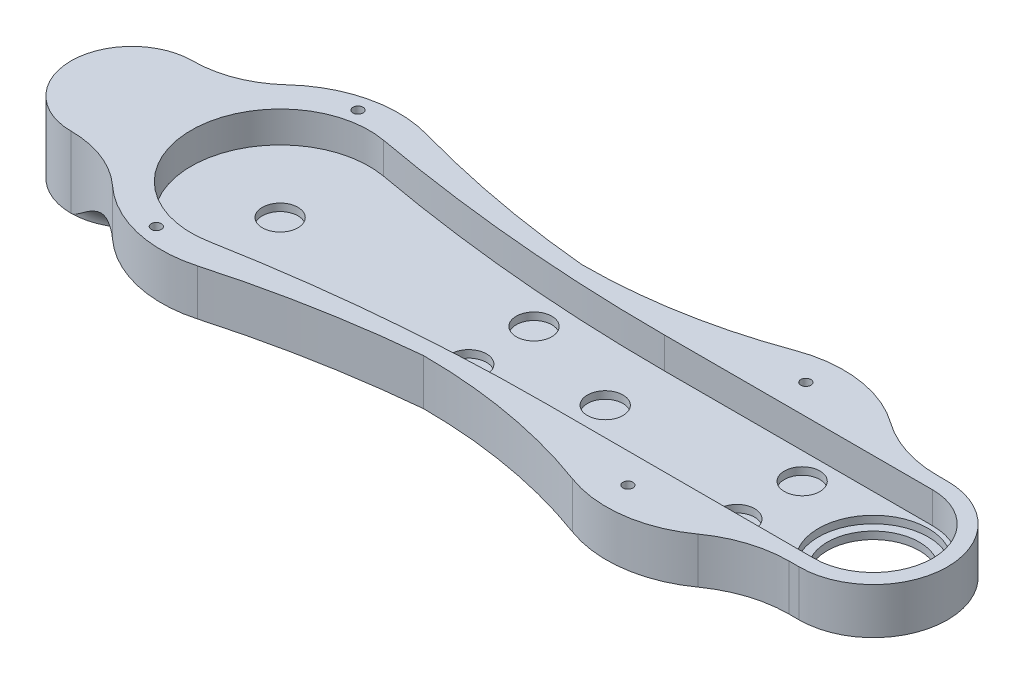
SolidWorks part; units mm, degrees
ref_plane "Front Plane" through (0, 0, 0) normal (0, 0, 1) x (1, 0, 0)
ref_plane "Top Plane" through (0, 0, 0) normal (0, 1, 0) x (1, 0, 0)
ref_plane "Right Plane" through (0, 0, 0) normal (1, 0, 0) x (0, 0, -1)
sketch "Sketch1" plane through (0, 0, 0) normal (0, 1, 0) x (1, 0, 0)
  line L0 (0, 0) -> (200, 0) construction
  line L1 (109.6, 25) -> (109.6, -25) construction
  line L2 (200, 25) -> (109.6, 25)
  line L3 (200, -25) -> (109.6, -25)
  line L4 (109.6, 20) -> (109.6, -20) construction
  line L5 (200, 20) -> (109.6, 20)
  line L6 (200, -20) -> (109.6, -20)
  circle A0 centre (0, 0) radius 30
  circle A1 centre (0, 0) radius 40
  circle A2 centre (109.6, 0) radius 25 construction
  circle A3 centre (200, 0) radius 25
  arc A4 (109.6, 25) -> (10.7476, 38.5291) centre (109.6, 392.9053) cw
  arc A5 (109.6, -25) -> (10.7476, -38.5291) centre (109.6, -392.9053) ccw
  circle A6 centre (109.6, 0) radius 20 construction
  circle A7 centre (200, 0) radius 20
  arc A8 (109.6, 20) -> (5.4293, 29.5046) centre (109.6, 595.608) cw
  arc A9 (109.6, -20) -> (5.4293, -29.5046) centre (109.6, -595.608) ccw
  dimension "D1" = 60
  dimension "D2" = 80
  dimension "D4" = 90.4
  dimension "D5" = 50
  dimension "D7" = 40
  dimension "D3" = 200
  dimension "D6" = 109.6
extrude "Boss-Extrude1" add sketch "Sketch1" along normal blind 10.5 contours A1 A9 A0 A8 | A8 L5 A3 L2 A4 A1 | L6 A9 A1 A5 L3 A3 | A7 L6 A3 L5 region at (100.5968, 0, -24.4026) region at (217.2249, 0, -17.2249) region at (21.2475, 0, -32.6216) region at (100.5968, 0, 24.4026)
sketch "Sketch4" plane through (0, 0, 0) normal (0, -1, 0) x (1, 0, 0)
  line L0 (200, 25) -> (109.6, 25) construction
  line L1 (200, -25) -> (109.6, -25) construction
  line L2 (200, 25) -> (109.6, 25)
  line L3 (200, -25) -> (109.6, -25)
  circle A0 centre (0, 0) radius 40 construction
  arc A1 (10.7476, 38.5291) -> (109.6, 25) centre (109.6, 392.9053) ccw construction
  circle A2 centre (200, 0) radius 25 construction
  arc A3 (109.6, -25) -> (10.7476, -38.5291) centre (109.6, -392.9053) ccw construction
  circle A4 centre (0, 0) radius 40
  arc A5 (10.7476, 38.5291) -> (109.6, 25) centre (109.6, 392.9053) ccw
  circle A6 centre (200, 0) radius 25
  arc A7 (109.6, -25) -> (10.7476, -38.5291) centre (109.6, -392.9053) ccw
  circle A8 centre (109.6, 0) radius 6
  circle A9 centre (200, 0) radius 18.5
  circle A10 centre (0, 0) radius 6
  arc M1 (10.7476, 38.5291) -> (10.7476, -38.5291) centre (0, 0) ccw
  arc M2 (10.7476, -38.5291) -> (109.6, -25) centre (109.6, -392.9053) cw
  line M3 (109.6, -25) -> (200, -25)
  arc M4 (200, -25) -> (200, 25) centre (200, 0) ccw
  line M5 (200, 25) -> (109.6, 25)
  arc M6 (109.6, 25) -> (10.7476, 38.5291) centre (109.6, 392.9053) cw
  arc M7 (10.7476, 38.5291) -> (10.7476, -38.5291) centre (0, 0) ccw
  arc M8 (5.4293, 29.5046) -> (109.6, 20) centre (109.6, 595.608) ccw
  line M9 (109.6, 20) -> (200, 20)
  arc M10 (200, 20) -> (200, -20) centre (200, 0) cw
  line M11 (200, -20) -> (109.6, -20)
  arc M12 (109.6, -20) -> (5.4293, -29.5046) centre (109.6, -595.608) ccw
  arc M27 (5.4293, -29.5046) -> (5.4293, 29.5046) centre (0, 0) cw
  dimension "D1" = 12
  dimension "D2" = 37
  dimension "D3" = 12
extrude "Boss-Extrude4" add sketch "Sketch4" along normal blind 5 contours A6 A4 A8 M9 M8 M12 M11 | A6 A9 M9 M11 M10 | A6 M4 M9 M10 M11 | A6 M5 M6 M7 M8 M9 | A6 M11 M12 M1 M2 M3 | A4 A10 M12 M8 M27 | A4 M7 M12 M27 M8 region at (100.5968, 0, 24.4026) region at (217.2249, 0, 17.2249) region at (192.5, 0, 19.3979) region at (173.3773, 0, 0) region at (21.2475, 0, 32.6216) region at (100.5968, 0, -24.4026) region at (36.7872, 0, 13.1831)
sketch "Sketch6" plane through (0, -5, 0) normal (0, -1, 0) x (1, 0, 0)
  circle A0 centre (109.6, 0) radius 6 construction
  circle A1 centre (109.6, 0) radius 6
  circle A3 centre (0, 0) radius 6 construction
  circle A4 centre (0, 0) radius 6
  circle A5 centre (200, 0) radius 18.5 construction
  circle A6 centre (200, 0) radius 18.5
  circle A7 centre (200, 0) radius 15.5
  dimension "D1" = 31
extrude "Boss-Extrude5" add sketch "Sketch6" against normal blind 2.5
sketch "Sketch8" plane through (0, -5, 0) normal (0, -1, 0) x (1, 0, 0)
  line L0 (200, 0) -> (-50, 0) construction
  line L1 (-50, -20.5) -> (-50, 20.5) construction
  circle A0 centre (-50, 0) radius 15.5
  circle A1 centre (-50, 0) radius 20.5
  arc A2 (-50, -20.5) -> (-27.081, -29.4384) centre (-50, -54.3526) cw
  arc A3 (10.7476, 38.5291) -> (10.7476, -38.5291) centre (0, 0) ccw construction
  arc A4 (-50, 20.5) -> (-27.081, 29.4384) centre (-50, 54.3526) ccw
  arc M7 (10.7476, 38.5291) -> (10.7476, -38.5291) centre (0, 0) ccw
  dimension "D1" = 31
  dimension "D2" = 41
  dimension "D3" = 250
extrude "Boss-Extrude9" add sketch "Sketch8" along normal blind 4.5 contours A1 A0 | A1 A0 M7 region at (-33.8188, -5, 0) region at (-66.0307, -5, 0)
extrude "Boss-Extrude11" add sketch "Sketch8<3>" against normal up to surface (15.5 mm away) contours A1 A2 M7 | A1 A0 M7 | A0 M7 | A4 A1 M7 region at (-51.4574, -5, 0) region at (-66.0307, -5, 0) region at (-37.7154, -5, 20.8507) region at (-37.7154, -5, -20.8507) up to face at (102.3377, 10.5, 0)
sketch "Sketch8<3>" plane through (0, -5, 0) normal (0, -1, 0) x (1, 0, 0) same geometry as "Sketch8"
sketch "Sketch9" plane through (0, -9.5, 0) normal (0, -1, 0) x (1, 0, 0)
  circle A0 centre (-50, 0) radius 20.5 construction
  circle A1 centre (-50, 0) radius 20.5
  circle A2 centre (-50, 0) radius 18.5
  dimension "D1" = 37
extrude "Boss-Extrude10" add sketch "Sketch9" along normal blind 4
fillet "Fillet1" radius 10 1 edges at (-29.5, -5, 0)
sketch "Sketch10" plane through (0, -5, 0) normal (0, -1, 0) x (1, 0, 0)
  circle A0 centre (-50, 0) radius 15.5 construction
  circle A1 centre (-50, 0) radius 15.5
extrude "Cut-Extrude1" cut sketch "Sketch10" against normal blind 11.5
sketch "Sketch11" plane through (0, -5, 0) normal (0, -1, 0) x (1, 0, 0)
  line L0 (200, 0) -> (-50, 0) construction
  line L1 (75, -26.6306) -> (75, 26.6306) construction
  line L2 (109.6, -25) -> (200, -25) construction
  line L3 (109.6, -25) -> (200, -25)
  line L4 (200, 25) -> (109.6, 25) construction
  line L5 (200, 25) -> (109.6, 25)
  circle A0 centre (0, 0) radius 40
  arc A1 (-27.081, -29.4384) -> (10.7476, -38.5291) centre (0, 0) ccw construction
  circle A2 centre (150, 0) radius 40
  arc A3 (109.6, -25) -> (10.7476, -38.5291) centre (109.6, -392.9053) ccw construction
  arc A4 (75, -26.6306) -> (136.1785, -37.5362) centre (75, -203.6839) cw
  arc A5 (75, 26.6306) -> (136.1785, 37.5362) centre (75, 203.6839) ccw
  arc A6 (10.7476, 38.5291) -> (109.6, 25) centre (109.6, 392.9053) ccw construction
  arc A7 (10.7476, 38.5291) -> (109.6, 25) centre (109.6, 392.9053) ccw
  arc A8 (109.6, -25) -> (10.7476, -38.5291) centre (109.6, -392.9053) ccw
  point P6 (75, 0)
  arc M7 (10.7476, -38.5291) -> (109.6, -25) centre (109.6, -392.9053) cw
  line M8 (109.6, -25) -> (200, -25)
  line M10 (200, 25) -> (109.6, 25)
  arc M11 (109.6, 25) -> (10.7476, 38.5291) centre (109.6, 392.9053) cw
extrude "Boss-Extrude12" add sketch "Sketch11" against normal up to surface (15.5 mm away) contours A2 L3 | A2 L5 | A4 A2 M7 M8 | A5 A2 M11 M10 region at (109.3141, -5, -28.2095) region at (150, -5, -31.1083) region at (150, -5, 31.1083) region at (109.3141, -5, 28.2095) up to face at (48.9434, 10.5, 0)
fillet "Fillet2" radius 40 2 edges at (181.225, 2.75, 25) (181.225, 2.75, -25)
sketch "Sketch12" plane through (0, -5, 0) normal (0, 1, 0) x (1, 0, 0)
  line L1 (200, 20) -> (109.6, 20) construction
  line L2 (200, -20) -> (109.6, -20) construction
  line L3 (225, 0) -> (-70.5, 0) construction
  line L4 (77.25, -43.0302) -> (77.25, 43.0302) construction
  arc A9 (200, -25) -> (200, 25) centre (200, 0) ccw construction
  arc A10 (-50, 20.5) -> (-50, -20.5) centre (-50, 0) ccw construction
  point P0 (147.25, 30)
  point P1 (147.25, -30)
  point P4 (-7.75, 34)
  point P17 (77.25, 0)
  point P18 (-7.75, -34)
  dimension "D1" = 10
  dimension "D2" = 10
  dimension "D3" = 70
  dimension "D4" = 34
  dimension "D5" = 34
  dimension "D6" = 85
hole_wizard "CBORE for M3 Hexagon head bolts-Full thread-grades AB1" positions "3DSketch1" profile "Sketch13" counterbore size "M3" standard "GB" end condition through all
sketch3d "3DSketch1"
  point P0 (147.25, -5, 30)
  point P2 (147.25, -5, -30)
  point P4 (-7.75, -5, 34)
  point P6 (-7.75, -5, -34)
sketch "Sketch13" plane through (147.25, -5, 30) normal (1, 0, 0) x (0, 0, -1)
  line L0 (0, 0) -> (0, 15.5)
  line L1 (0, 15.5) -> (1.7, 15.5)
  line L3 (1.7, 15.5) -> (1.7, 2)
  line L4 (1.7, 2) -> (3.5, 2)
  line L5 (3.5, 2) -> (3.5, 0)
  line L7 (3.5, 0) -> (0, 0)
  line L11 (0, -6.35) -> (0, 107.95) construction
  dimension "Thru Hole Dia." = 3.4
  dimension "Thru Hole Depth" = 15.5
  dimension "C'Bore Dia." = 7
  dimension "C'Bore Depth" = 2
sketch "Sketch14" plane through (0, 0, 0) normal (0, 1, 0) x (1, 0, 0)
  line L0 (109.6, 0) -> (54.5654, 0) construction
  circle A0 centre (74.6, -11) radius 6
  circle A1 centre (74.6, 11) radius 6
  circle A2 centre (165, -11) radius 6
  circle A3 centre (165, 11) radius 6
  circle A4 centre (109.6, 0) radius 6 construction
  circle A5 centre (200, 0) radius 18.5 construction
  dimension "D1" = 35
  dimension "D2" = 35
  dimension "D4" = 22
  dimension "D3" = 11
extrude "Cut-Extrude2" cut sketch "Sketch14" against normal blind 2.5
